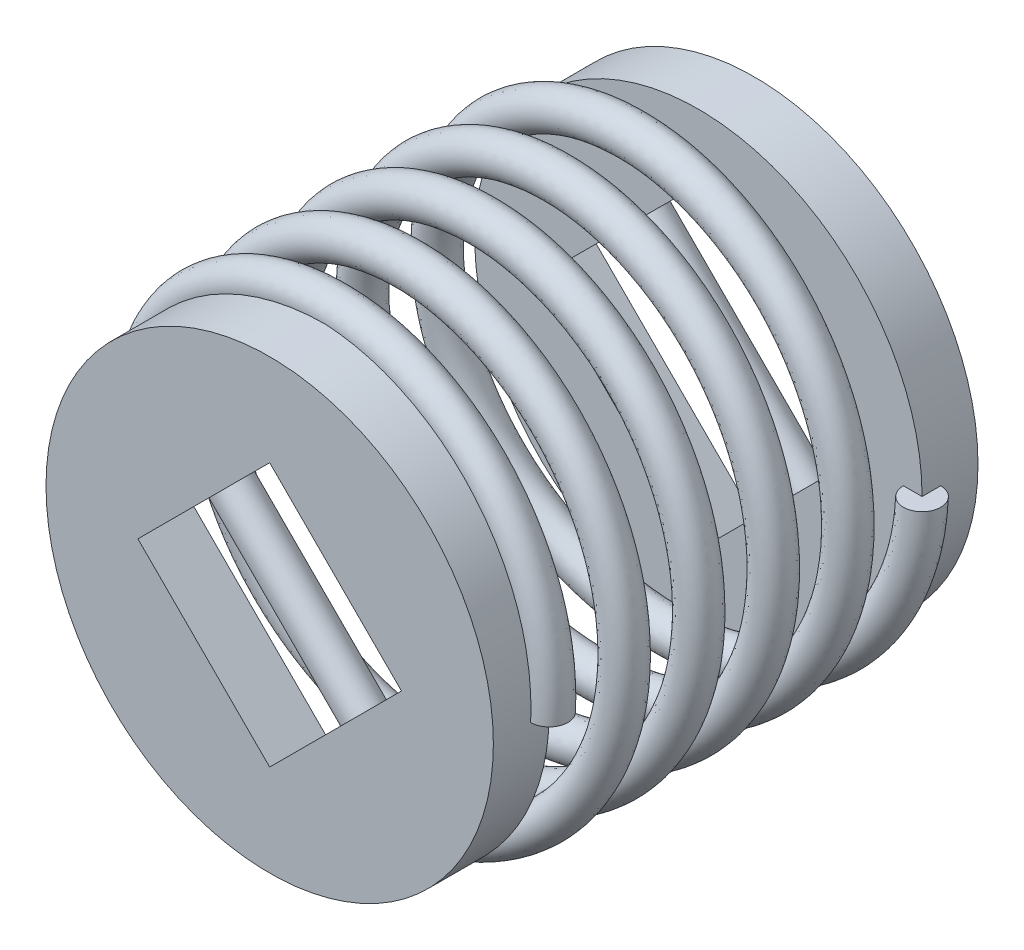
SolidWorks part; units mm, degrees
ref_plane "前视基准面" through (0, 0, 0) normal (0, 0, 1) x (1, 0, 0)
ref_plane "上视基准面" through (0, 0, 0) normal (0, 1, 0) x (1, 0, 0)
ref_plane "右视基准面" through (0, 0, 0) normal (1, 0, 0) x (0, 0, -1)
sketch "草图1" plane through (0, 0, 0) normal (0, 0, 1) x (1, 0, 0)
  circle A0 centre (0, 0) radius 12
curve "螺旋线/涡状线1" pitch 4 height 20 radius 12 left hand yes centre (0, 0, 0) axis (0, 0, 1) start towards (1, 0, 0)
sketch "草图2" plane through (0, 0, 0) normal (0, 1, 0) x (1, 0, 0)
  circle A0 centre (11.9988, 0) radius 1
sweep "扫描1" add profiles "草图2" path "螺旋线/涡状线1"
sketch "草图3" plane through (0, 0, 0) normal (0, 0, 1) x (1, 0, 0)
  circle A0 centre (0, 0) radius 12
extrude "凸台-拉伸2" add sketch "草图3" against normal blind 3 contours A0
sketch "草图4" plane through (0, 0, 0) normal (0, 0, 1) x (1, 0, 0)
  circle A0 centre (0, 0) radius 1
extrude "凸台-拉伸3" add sketch "草图4" along normal blind 20
sketch "草图5" plane through (0, 0, 20) normal (0, 0, 1) x (1, 0, 0)
  circle A0 centre (0, 0) radius 12
extrude "凸台-拉伸4" add sketch "草图5" along normal blind 3
sketch "草图6" plane through (0, 0, -3) normal (0, 0, -1) x (-1, 0, 0)
  line L0 (0, 8.484) -> (-8.484, 0)
  line L1 (-8.484, 0) -> (0, -8.484)
  line L2 (0, -8.484) -> (8.484, 0)
  line L3 (8.484, 0) -> (0, 8.484)
  circle A0 centre (0, 0) radius 8.484
extrude "切除-拉伸1" cut sketch "草图6" against normal blind 26 contours L2 L3 L0 L1 region at (0, 0, -3)
sketch "草图7" plane through (-4.242, 4.242, 0) normal (0.7071, -0.7071, 0) x (0, 0, -1)
  line L0 (3, -5.9991) -> (3, 5.9991) construction
  circle A0 centre (1.5, 0) radius 1
  point P0 (3, 0)
  point P7 (1.5, 0)
extrude "凸台-拉伸5" add sketch "草图7" along normal blind 12
sketch "草图8" plane through (4.242, -4.242, 0) normal (-0.7071, 0.7071, 0) x (0, 0, 1)
  circle A0 centre (21.5, 0) radius 1
  point P6 (21.5, 0)
extrude "凸台-拉伸6" add sketch "草图8" along normal blind 12
sketch "草图9" plane through (0, 0, 23) normal (0, 0, 1) x (1, 0, 0)
  line L0 (4.242, 4.242) -> (-4.242, -4.242)
  line L1 (0, 8.484) -> (8.484, 0) construction
  line L2 (0, -8.484) -> (-8.484, 0) construction
  line L3 (4.242, 4.242) -> (3.5349, 3.5349)
  line L4 (3.5349, 3.5349) -> (0, 7.0698)
  line L5 (0, 7.0698) -> (-7.0698, 0)
  line L6 (-7.0698, 0) -> (0, -7.0698)
  line L7 (0, -7.0698) -> (7.0698, 0)
  line L8 (7.0698, 0) -> (3.5349, 3.5349)
  line L11 (0, -8.484) -> (8.484, 0)
  line L12 (8.484, 0) -> (0, 8.484)
  line L13 (0, 8.484) -> (-8.484, 0)
  line L14 (-8.484, 0) -> (0, -8.484)
  point P6 (0, 0)
  line M3 (0, -8.484) -> (-8.484, 0)
  line M4 (-8.484, 0) -> (0, 8.484)
  line M5 (0, 8.484) -> (8.484, 0)
  line M6 (8.484, 0) -> (0, -8.484)
extrude "凸台-拉伸7" add sketch "草图9" against normal blind 3 contours L6 L5 L4 L0 M5 M4 M3 | L8 L7 L6 L0 M3 M6 M5 region at (6.2357, 1.9937, 23) region at (3.7612, 4.0157, 23)
